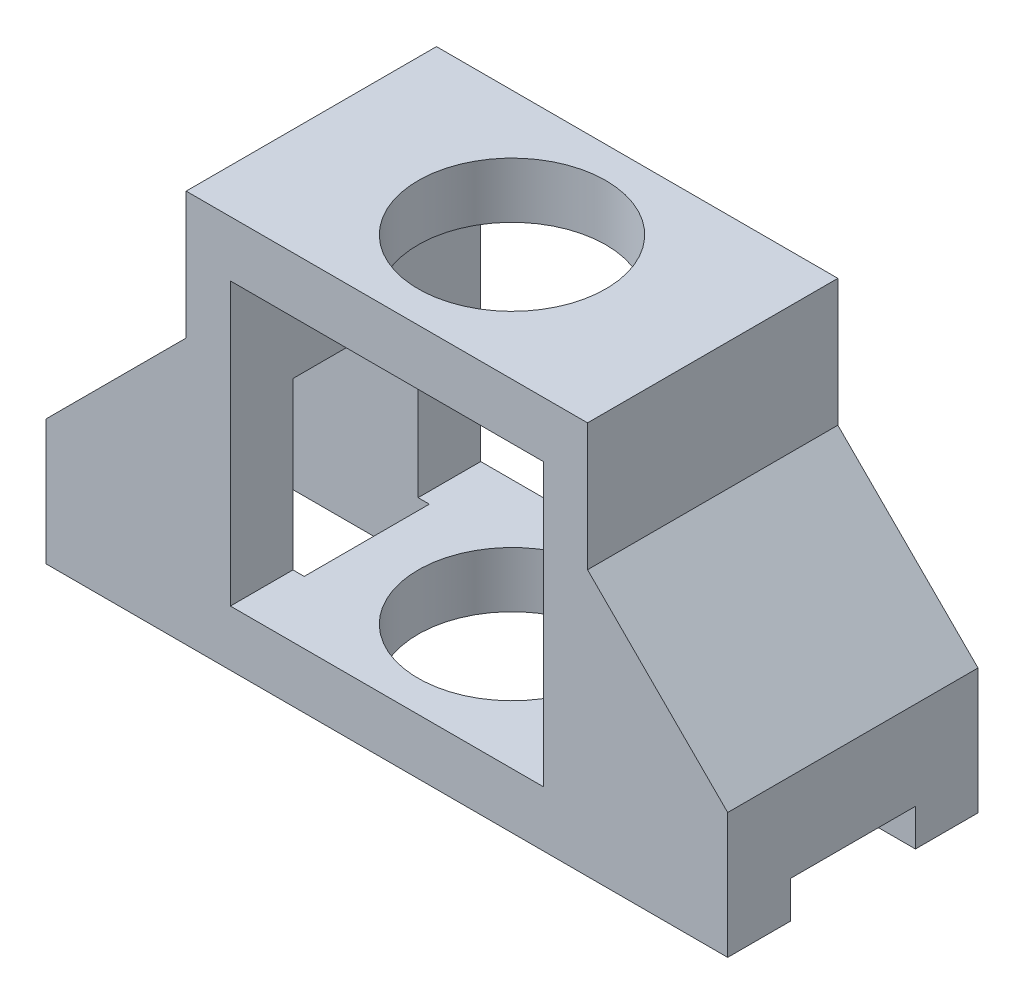
SolidWorks part; units mm, degrees
ref_plane "Front Plane" through (0, 0, 0) normal (0, 0, 1) x (1, 0, 0)
ref_plane "Top Plane" through (0, 0, 0) normal (0, 1, 0) x (1, 0, 0)
ref_plane "Right Plane" through (0, 0, 0) normal (1, 0, 0) x (0, 0, -1)
sketch "Sketch2" plane through (0, 0, 0) normal (0, 1, 0) x (1, 0, 0)
  circle A0 centre (0, 0) radius 19.05
  dimension "D1" = 38.1
extrude "Boss-Extrude1" add sketch "Sketch2" along normal blind 152.4
sketch "Sketch3" plane through (0, 0, 0) normal (0, 0, 1) x (1, 0, 0)
  line L0 (-6.0287, 90.0484) -> (11.9318, 72.0879)
  line L1 (-6.0287, 90.0484) -> (-409.7898, -313.7127)
  line L2 (11.9318, 72.0879) -> (-391.8293, -331.6732)
  line L3 (-409.7898, -313.7127) -> (-391.8293, -331.6732)
  line L4 (-19.05, 152.4) -> (-19.05, 0) construction
  line L5 (-391.8293, -331.6732) -> (-427.7503, -331.6732)
  line L6 (-427.7503, -331.6732) -> (-409.7898, -313.7127)
  line L7 (19.05, 152.4) -> (-19.05, 152.4) construction
  point P6 (-340.3267, -147.3931)
  point P11 (0, 85.5308)
  point P12 (0, 0)
  dimension "D1" = 135
  dimension "D2" = 25.4
  dimension "D3" = 484.0732
  dimension "D4" = 391.8293
extrude "Boss-Extrude2" add sketch "Sketch3" along normal mid plane 25.4 contours L6 L5 L3 | L1 L3 L2 L0 region at (-198.929, -120.8124, 0) region at (-409.7898, -325.6864, 0)
mirror "Mirror1" about plane through (0, 0, 0) normal (1, 0, 0) of "Boss-Extrude2"
ref_plane "Plane1" through (0, 0, 25.4) normal (0, 0, 1) x (1, 0, 0)
sketch "Sketch4" plane through (0, 0, 25.4) normal (0, 0, 1) x (1, 0, 0)
  line L0 (0, -20.955) -> (0, 20.955) construction
  line L1 (69.1731, 19.3936) -> (-69.1731, 19.3936)
  line L2 (69.1731, 19.3936) -> (69.1731, 99.1255)
  line L3 (69.1731, 99.1255) -> (-69.1731, 99.1255)
  line L4 (-69.1731, 19.3936) -> (-69.1731, 99.1255)
  line L5 (69.1731, 19.3936) -> (-69.1731, 99.1255) construction
  line L6 (69.1731, 99.1255) -> (-69.1731, 19.3936) construction
  point P0 (0, 59.2596)
  point P5 (0, 40.4638)
  point P6 (0, 37.7799)
  point P7 (155.0298, 0)
  point P10 (109.4042, 0)
  point P11 (0, 0)
  point P12 (0, 59.2596)
extrude "Boss-Extrude3" add sketch "Sketch4" against normal blind 50.8 separate body
combine bodies "Combine1" operation type subtract main body 104 bodies to subtract 103
sketch "Sketch5" plane through (0, 0, 25.4) normal (0, 0, 1) x (1, 0, 0)
  line L0 (-69.1731, 99.1255) -> (-69.1731, 19.3936) construction
  line L1 (-31.75, 30.6846) -> (31.75, 30.6846)
  line L2 (-31.75, 30.6846) -> (-31.75, 87.8346)
  line L3 (-31.75, 87.8346) -> (31.75, 87.8346)
  line L4 (31.75, 30.6846) -> (31.75, 87.8346)
  line L5 (-31.75, 30.6846) -> (31.75, 87.8346) construction
  line L6 (-31.75, 87.8346) -> (31.75, 30.6846) construction
  line L7 (69.1731, 99.1255) -> (-69.1731, 99.1255) construction
  point P0 (0, 59.2596)
  point P7 (-69.1731, 59.2596)
  point P10 (0, 99.1255)
  dimension "D1" = 63.5
  dimension "D2" = 57.15
extrude "Cut-Extrude1" cut sketch "Sketch5" against normal through all
sketch "Sketch6" plane through (0, 0, 25.4) normal (0, 0, 1) x (1, 0, 0)
  line L0 (-69.1731, 26.904) -> (-31.75, 64.3271) construction
  line L1 (-69.1731, 26.904) -> (-31.75, 64.3271)
  line L2 (-69.1731, 44.8645) -> (-40.7303, 73.3074)
  line L3 (-40.7303, 73.3074) -> (-40.7303, 99.1255)
  line L4 (-78.1534, 35.8842) -> (-40.7303, 73.3074) construction
  line L6 (-69.1731, 99.1255) -> (-69.1731, 19.3936)
  line L7 (-69.1731, 19.3936) -> (69.1731, 19.3936)
  line L8 (69.1731, 19.3936) -> (69.1731, 99.1255)
  line L9 (69.1731, 99.1255) -> (-69.1731, 99.1255)
  line L10 (-69.1731, 99.1255) -> (-69.1731, 19.3936)
  line L11 (-69.1731, 19.3936) -> (69.1731, 19.3936)
  line L12 (69.1731, 19.3936) -> (69.1731, 99.1255)
  line L13 (69.1731, 99.1255) -> (-69.1731, 99.1255)
  point P9 (-69.1731, 44.8411)
  point P11 (-69.1731, 44.8645)
  line M10 (-69.1731, 99.1255) -> (-69.1731, 19.3936)
  line M13 (69.1731, 99.1255) -> (-69.1731, 99.1255)
  dimension "D1" = 0
  dimension "D2" = 12.7
extrude "Cut-Extrude2" cut sketch "Sketch6" against normal through all contours L2 L3 M13 M10 region at (-56.6354, 78.2638, 25.4)
mirror "Mirror2" about plane through (0, 0, 0) normal (1, 0, 0) of "Cut-Extrude2"
